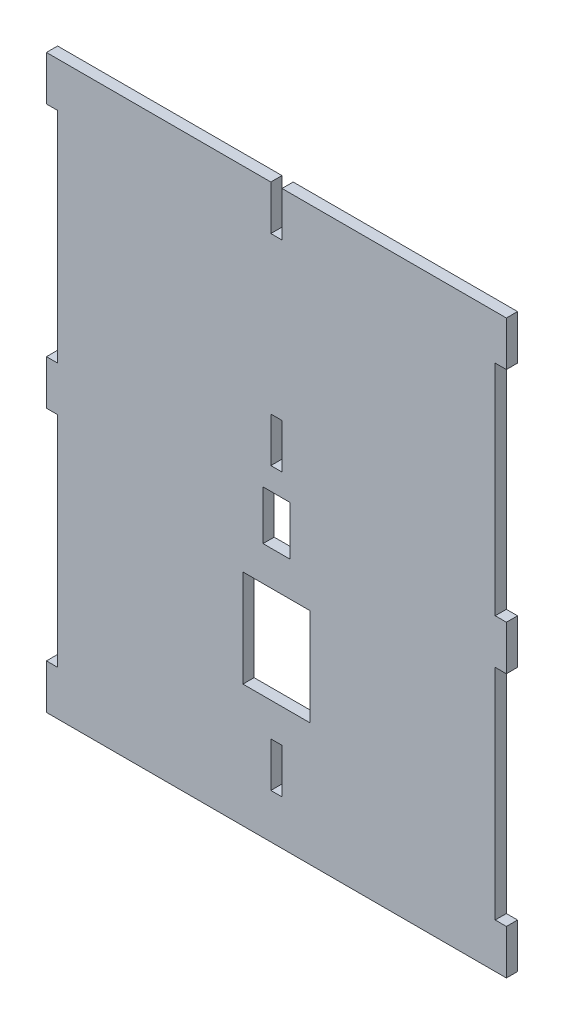
SolidWorks part; units mm, degrees
ref_plane "Plan de face" through (0, 0, 0) normal (0, 0, 1) x (1, 0, 0)
ref_plane "Plan de dessus" through (0, 0, 0) normal (0, 1, 0) x (1, 0, 0)
ref_plane "Plan de droite" through (0, 0, 0) normal (1, 0, 0) x (0, 0, -1)
sketch "Esquisse1" plane through (0, 0, 0) normal (0, 0, 1) x (1, 0, 0)
  line L0 (2.5, -90) -> (-2.5, -90)
  line L1 (103, 0) -> (103, -20)
  line L2 (103, -20) -> (98, -20)
  line L3 (98, -20) -> (98, -118)
  line L4 (98, -118) -> (103, -118)
  line L5 (103, -118) -> (103, -138)
  line L6 (103, -138) -> (98, -138)
  line L7 (98, -138) -> (98, -236)
  line L8 (98, -236) -> (103, -236)
  line L9 (103, -236) -> (103, -256)
  line L10 (103, -256) -> (-103, -256)
  line L11 (0, -256) -> (0, -236) construction
  line L12 (-2.5, -236) -> (2.5, -236)
  line L13 (2.5, -236) -> (2.5, -216)
  line L14 (2.5, -216) -> (-2.5, -216)
  line L15 (0, -216) -> (0, -201) construction
  line L16 (-15, -201) -> (15, -201)
  line L17 (15, -201) -> (15, -157.5)
  line L18 (15, -157.5) -> (-15, -157.5)
  line L19 (0, -157.5) -> (0, -142) construction
  line L20 (-6, -142) -> (6, -142)
  line L21 (6, -142) -> (6, -120)
  line L22 (6, -120) -> (-6, -120)
  line L23 (0, -120) -> (0, -110) construction
  line L24 (-2.5, -110) -> (2.5, -110)
  line L25 (2.5, -110) -> (2.5, -90)
  line L26 (0, -90) -> (0, -20) construction
  line L27 (-2.5, -20) -> (2.5, -20)
  line L28 (2.5, -20) -> (2.5, 0)
  line L29 (2.5, 0) -> (103, 0)
  line L30 (-2.5, -20) -> (-2.5, 0)
  line L31 (-2.5, -110) -> (-2.5, -90)
  line L32 (-6, -142) -> (-6, -120)
  line L33 (-15, -201) -> (-15, -157.5)
  line L34 (-2.5, -236) -> (-2.5, -216)
  line L35 (-103, -236) -> (-103, -256)
  line L36 (-98, -236) -> (-103, -236)
  line L37 (-98, -138) -> (-98, -236)
  line L38 (-103, -138) -> (-98, -138)
  line L39 (-103, -118) -> (-103, -138)
  line L40 (-98, -118) -> (-103, -118)
  line L41 (-98, -20) -> (-98, -118)
  line L42 (-103, -20) -> (-98, -20)
  line L43 (-103, 0) -> (-103, -20)
  line L44 (-2.5, 0) -> (-103, 0)
  dimension "D1" = 103
  dimension "D2" = 20
  dimension "D3" = 98
  dimension "D4" = 5
  dimension "D5" = 15
  dimension "D6" = 2.5
  dimension "D7" = 15.5
  dimension "D8" = 43.5
  dimension "D9" = 15
  dimension "D10" = 22
  dimension "D11" = 10
  dimension "D12" = 6
extrude "Boss.-Extru.1" add sketch "Esquisse1" along normal blind 5
equation "\"D\"=6"
